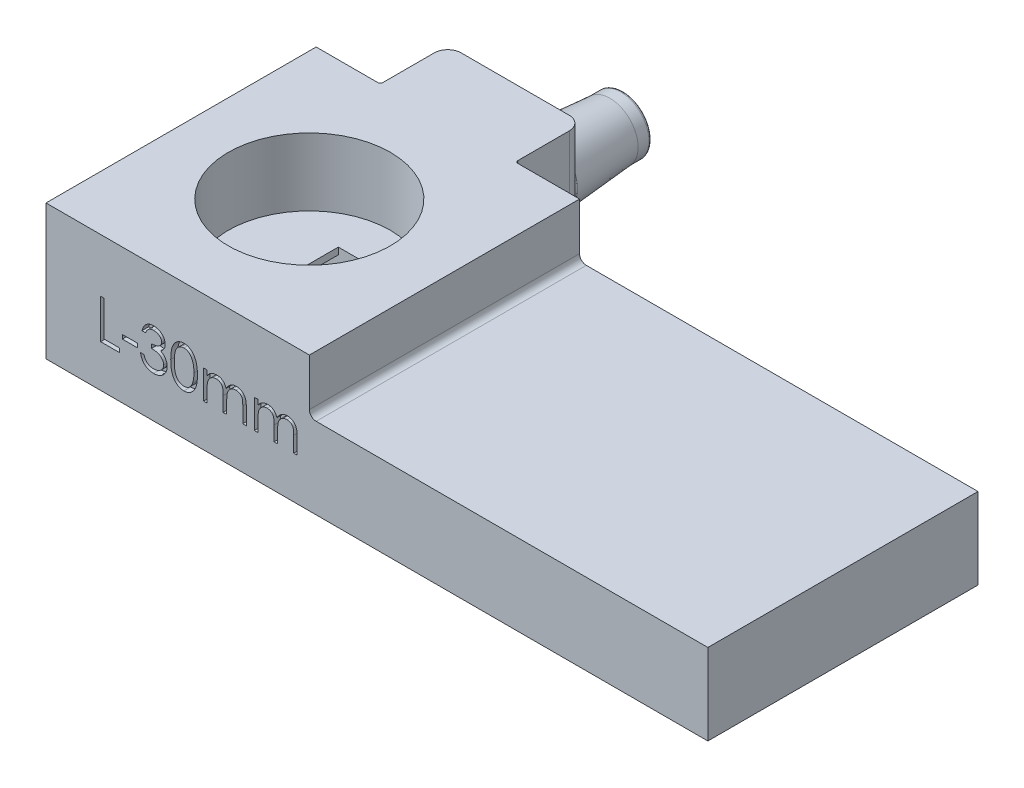
SolidWorks part; units mm, degrees
ref_plane "Front Plane" through (0, 0, 0) normal (0, 0, 1) x (1, 0, 0)
ref_plane "Top Plane" through (0, 0, 0) normal (0, 1, 0) x (1, 0, 0)
ref_plane "Right Plane" through (0, 0, 0) normal (1, 0, 0) x (0, 0, -1)
sketch "Sketch2" plane through (0, 0, 0) normal (0, 1, 0) x (1, 0, 0)
  line L1 (-14.4231, 13.5577) -> (34.5769, 13.5577)
  line L2 (-14.4231, 13.5577) -> (-14.4231, -6.4423)
  line L3 (-14.4231, -6.4423) -> (34.5769, -6.4423)
  line L4 (34.5769, 13.5577) -> (34.5769, -6.4423)
  dimension "D1" = 49
  dimension "D2" = 20
extrude "Boss-Extrude1" add sketch "Sketch2" along normal blind 10
sketch "Sketch3" plane through (0, 0, 0) normal (0, -1, 0) x (1, 0, 0)
  line L0 (34.5769, 6.4423) -> (34.5769, -13.5577) construction
  line L1 (27.5769, -5.0677) -> (-2.4231, -5.0677)
  line L2 (27.5769, -5.0677) -> (27.5769, -2.0477)
  line L3 (27.5769, -2.0477) -> (-2.4231, -2.0477)
  line L4 (-2.4231, -5.0677) -> (-2.4231, -2.0477)
  line L5 (-14.4231, -3.5577) -> (34.5769, -3.5577) construction
  line L6 (-14.4231, -13.5577) -> (-14.4231, 6.4423) construction
  dimension "D1" = 30
  dimension "D2" = 7
  dimension "D3" = 3.02
  dimension "D4" = 1.51
extrude "Cut-Extrude1" cut sketch "Sketch3" against normal blind 2
sketch "Sketch4" plane through (0, 0, 0) normal (0, -1, 0) x (1, 0, 0)
  line L0 (-2.4231, -2.0477) -> (-2.4231, -5.0677) construction
  line L1 (-2.4231, -6.5477) -> (-7.4231, -6.5477)
  line L2 (-2.4231, -6.5477) -> (-2.4231, -0.5477)
  line L3 (-2.4231, -0.5477) -> (-7.4231, -0.5477)
  line L4 (-7.4231, -6.5477) -> (-7.4231, -0.5477)
  line L6 (27.5769, -2.0477) -> (-2.4231, -2.0477) construction
  dimension "D1" = 6
  dimension "D2" = 5
  dimension "D3" = 1.5
extrude "Cut-Extrude2" cut sketch "Sketch4" against normal blind 5
sketch "Sketch5" plane through (0, 5, 0) normal (0, -1, 0) x (1, 0, 0)
  line L0 (-7.4231, -3.5477) -> (-2.4231, -3.5577) construction
  line L1 (-7.4231, -0.5477) -> (-7.4231, -6.5477) construction
  line L2 (-2.4231, -2.0477) -> (-2.4231, -5.0677) construction
  circle A0 centre (-4.9231, -3.5527) radius 6
  dimension "D1" = 12
extrude "Cut-Extrude3" cut sketch "Sketch5" against normal through all
sketch "Sketch6" plane through (0, 5, 0) normal (0, 1, 0) x (1, 0, 0)
  line L0 (-4.0731, 0.5477) -> (-2.4231, 0.5477)
  line L1 (-7.4231, 6.5477) -> (-5.7731, 6.5477)
  line L2 (-7.4231, 6.5477) -> (-7.4231, 0.5477)
  line L3 (-7.4231, 0.5477) -> (-5.7731, 0.5477)
  line L4 (-2.4231, 6.5477) -> (-2.4231, 0.5477)
  line L5 (-4.0731, 6.5477) -> (-2.4231, 6.5477)
  line L7 (-5.7731, 6.5477) -> (-5.7731, 0.5477)
  line L9 (-4.0731, 6.5477) -> (-4.0731, 0.5477)
  dimension "D1" = 1.7
extrude "Boss-Extrude2" add sketch "Sketch6" against normal blind 0.5
sketch "Sketch11" plane through (0, 0, 0) normal (0, -1, 0) x (1, 0, 0)
  circle A0 centre (28.8884, -3.5577) radius 2
  dimension "D1" = 4
extrude "Cut-Extrude4" cut sketch "Sketch11" against normal up to surface (2 mm away) up to face at (12.5769, 2, -3.5577)
sketch "Sketch12" plane through (0, 0, 0) normal (0, -1, 0) x (1, 0, 0)
  line L1 (-7.4231, -0.5477) -> (-2.4231, -0.5477)
  line L2 (-7.4231, -0.5477) -> (-7.4231, -6.5477)
  line L3 (-7.4231, -6.5477) -> (-2.4231, -6.5477)
  line L4 (-2.4231, -0.5477) -> (-2.4231, -6.5477)
extrude "Boss-Extrude4" add sketch "Sketch12" against normal blind 0.8
sketch "Sketch14" plane through (0, 0, 6.4423) normal (0, 0, 1) x (1, 0, 0)
  line L0 (-14.4231, 10) -> (34.5769, 10) construction
  line L1 (5.0769, 10) -> (34.5769, 10)
  line L2 (5.0769, 10) -> (5.0769, 6)
  line L3 (5.0769, 6) -> (34.5769, 6)
  line L4 (34.5769, 10) -> (34.5769, 6)
  line L5 (34.5769, 10) -> (34.5769, 0) construction
  line L6 (27.5769, 2) -> (-2.4231, 2) construction
  line L7 (1.0769, 5) -> (1.0769, 10) construction
  dimension "D1" = 4
  dimension "D2" = 4
extrude "Cut-Extrude6" cut sketch "Sketch14" against normal through all
fillet "Fillet1" radius 0.5 1 edges at (5.0769, 6, -3.5577)
sketch "Sketch13" plane through (0, 0, 6.4423) normal (0, 0, 1) x (1, 0, 0)
  line L0 (-10.748, 3.1258) -> (12.5164, 3.1258) construction
  text T0 "L-30mm" font "Century Gothic" height in points 11
extrude "Cut-Extrude5" cut sketch "Sketch13" against normal blind 0.5
sketch "Sketch17" [suppressed] plane through (0, 0, -13.5577) normal (0, 0, -1) x (-1, 0, 0)
  line L0 (-3.1673, 3.3835) -> (11.793, 3.3835) construction
  text T0 "h-2mm"
sketch "Sketch19" plane through (0, 10, 0) normal (0, 1, 0) x (1, 0, 0)
  line L0 (5.0769, 13.5577) -> (-14.4231, 13.5577) construction
  line L1 (-9.6731, 18.5477) -> (0.3269, 18.5477)
  line L2 (-9.6731, 18.5477) -> (-9.6731, 13.5577)
  line L3 (-9.6731, 13.5577) -> (0.3269, 13.5577)
  line L4 (0.3269, 18.5477) -> (0.3269, 13.5577)
  line L6 (-4.6731, -6.4423) -> (-4.6731, 18.5477) construction
  line L8 (-14.4231, -6.4423) -> (5.0769, -6.4423) construction
  dimension "D1" = 10
  dimension "D3" = 12
extrude "Boss-Extrude5" add sketch "Sketch19" against normal up to surface (10 mm away) up to face at (13.4048, 0, -3.5577)
fillet "Fillet2" radius 1 2 edges at (-9.6731, 5, -18.5477) (0.3269, 5, -18.5477)
sketch "Sketch20" plane through (0, 0, -18.5477) normal (0, 0, -1) x (-1, 0, 0)
  line L0 (8.6731, 0) -> (0.6731, 0) construction
  circle A0 centre (4.6731, 3.5) radius 0.5
  dimension "D1" = 1
  dimension "D2" = 3.5
extrude "Cut-Extrude7" cut sketch "Sketch20" against normal up to next
sketch "Sketch21" plane through (0, 0, -18.5477) normal (0, 0, -1) x (-1, 0, 0)
  circle A0 centre (4.6731, 3.5) radius 1.4
  dimension "D1" = 2.8
extrude "Cut-Extrude8" cut sketch "Sketch21" against normal offset from surface (10 mm away) 2 up to face at (-5.1731, 3.5, -6.5477)
ref_axis "Axis1" through (-4.6731, 3.5, -8.5477) along (0, 0, -1)
ref_plane "Plane1" through (0, 3.5, 0) normal (0, -1, 0) x (-1, 0, 0)
sketch "Sketch23" plane through (0, 3.5, 0) normal (0, -1, 0) x (-1, 0, 0)
  line L0 (4.6731, 15.6131) -> (4.6731, 26.4829) construction
  line L1 (4.6731, 8.5477) -> (4.6731, 18.5477) construction
  line L2 (6.2731, 26.5477) -> (6.7731, 26.5477)
  line L3 (6.7731, 26.5477) -> (6.7731, 25.5477)
  line L4 (6.7731, 25.5477) -> (7.1731, 20.6558)
  line L5 (7.0734, 20.5477) -> (6.7731, 20.5477)
  line L6 (6.7731, 20.5477) -> (6.7731, 18.5477)
  line L7 (8.6731, 18.5477) -> (0.6731, 18.5477) construction
  line L8 (6.7731, 18.5477) -> (6.2731, 18.5477)
  line L9 (6.2731, 18.5477) -> (6.2731, 26.5477)
  arc A0 (7.0734, 20.5477) -> (7.1731, 20.6558) centre (7.0734, 20.6477) ccw
  dimension "D1" = 0.1
  dimension "D2" = 0.5
  dimension "D3" = 4.2
  dimension "D4" = 5
  dimension "D5" = 8
  dimension "D6" = 7
  dimension "D7" = 5
revolve "Revolve1" add sketch "Sketch23" angle 360 about L0
fillet "Fillet3" radius 0.2 5 edges at (-3.0731, 3.5, -26.5477) (-2.5731, 3.5, -26.5477) (-6.7731, 3.5, -18.5477)
